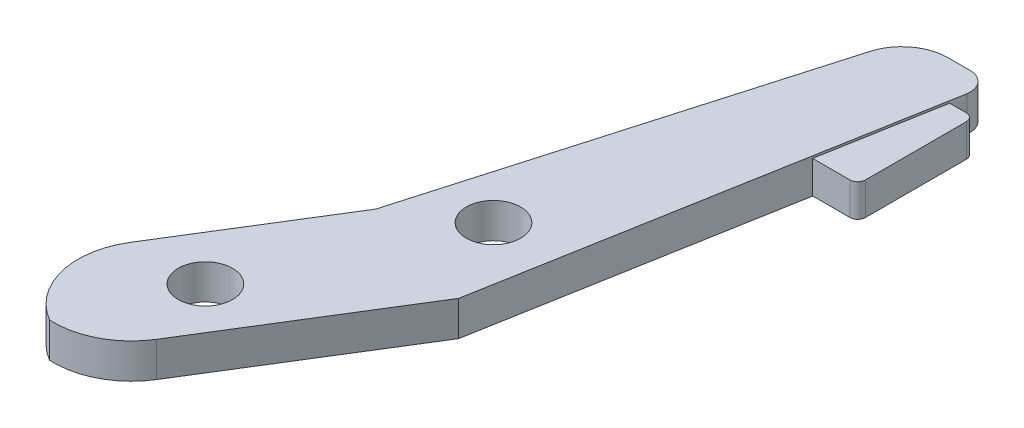
SolidWorks part; units mm, degrees
ref_plane "Front Plane" through (0, 0, 0) normal (0, 0, 1) x (1, 0, 0)
ref_plane "Top Plane" through (0, 0, 0) normal (0, 1, 0) x (1, 0, 0)
ref_plane "Right Plane" through (0, 0, 0) normal (1, 0, 0) x (0, 0, -1)
sketch "Sketch1" plane through (0, 0, 0) normal (0, 1, 0) x (1, 0, 0)
  line L0 (0, 0) -> (9.4812, 15.3005)
  line L1 (9.4812, 15.3005) -> (17.2343, 42.2057)
  line L6 (17.1409, 12.992) -> (7.6597, -2.3085)
  line L7 (7.6597, -2.3085) -> (0, 0)
  line L9 (17.1409, 12.992) -> (22.3475, 42.2057)
  line L10 (22.3475, 42.2057) -> (17.2343, 42.2057)
  dimension "D1" = 8
  dimension "D2" = 18
  dimension "D3" = 18
  dimension "D4" = 28
extrude "Boss-Extrude1" add sketch "Sketch1" along normal blind 2.25
fillet "Fillet1" radius 5 2 edges at (7.6597, 1.125, 2.3085) (0, 1.125, 0)
sketch "Sketch2" plane through (0, 2.25, 0) normal (0, 1, 0) x (1, 0, 0)
  line L0 (17.1409, 12.992) -> (22.3475, 42.2057) construction
  line L1 (9.6801, 0.952) -> (17.1409, 12.992) construction
  circle A0 centre (8.1672, 5.6299) radius 1.75
  circle A1 centre (14.0315, 18.3425) radius 1.75
  dimension "D1" = 3.5
  dimension "D2" = 3.5
  dimension "D3" = 14
  dimension "D4" = 4
  dimension "D5" = 3.75
extrude "Cut-Extrude1" cut sketch "Sketch2" against normal through all
ref_plane "Plane1" through (23.5, 0, 0) normal (1, 0, 0) x (0, 0, -1)
sketch "Sketch4" plane through (23.5, -1.4847, -8.2019) normal (1, 0, 0) x (0, 0, -1)
  line L1 (31.6585, 3.5919) -> (24.1585, 3.5919)
  line L2 (31.6585, 3.5919) -> (31.6585, 1.4919)
  line L3 (31.6585, 1.4919) -> (24.1585, 1.4919)
  line L4 (24.1585, 3.5919) -> (24.1585, 1.4919)
  dimension "D1" = 2.1
  dimension "D2" = 7.5
extrude "Boss-Extrude2" add sketch "Sketch4" against normal up to surface (1.5705 mm away) up to face at (19.7442, 1.125, -27.5989)
extrude "Boss-Extrude3" add sketch "Sketch4<2>" against normal up to surface (1.5705 mm away) up to face at (21.2611, 1.0572, -36.1104)
sketch "Sketch4<2>" plane through (23.5, -1.4847, -8.2019) normal (1, 0, 0) x (0, 0, -1) same geometry as "Sketch4"
fillet "Fillet2" radius 3 1 edges at (17.2343, 1.125, -42.2057)
fillet "Fillet3" radius 1.2 1 edges at (22.3475, 1.125, -42.2057)
fillet "Fillet4" radius 0.5 2 edges at (23.5, 1.0572, -32.3604) (23.5, 1.0572, -39.8604)
